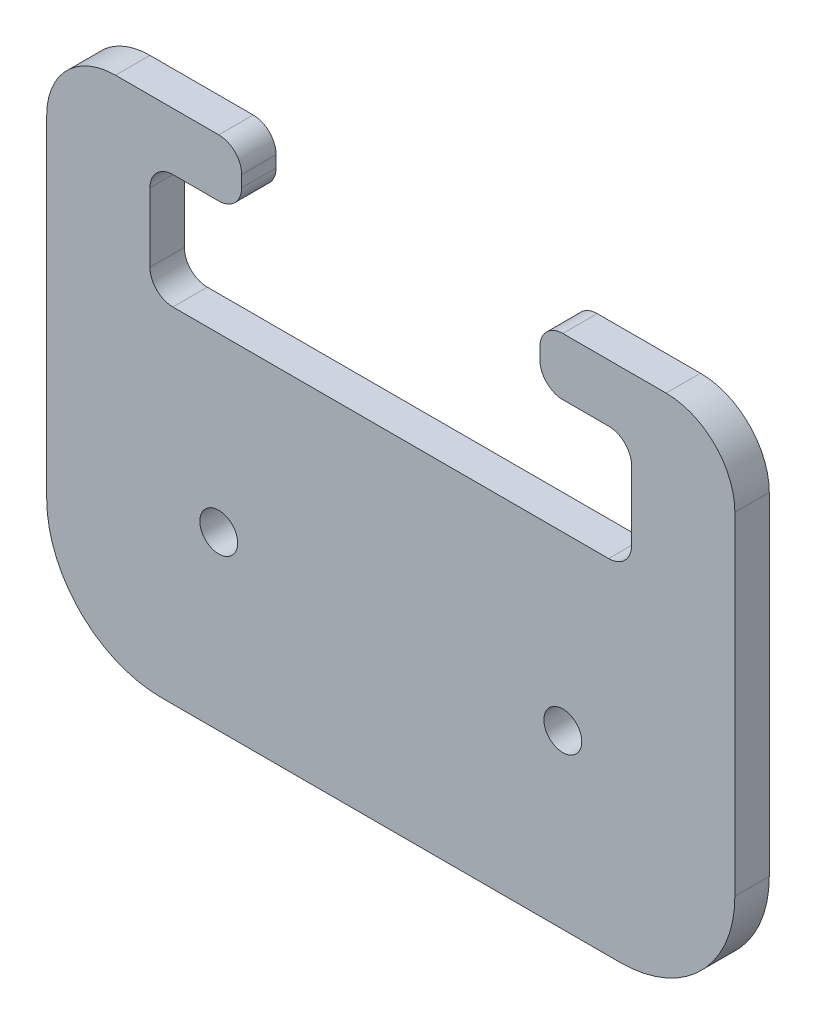
SolidWorks part; units mm, degrees
material "Hexcel AS4C (3000 丝)"
ref_plane "前视基准面" through (0, 0, 0) normal (0, 0, 1) x (1, 0, 0)
ref_plane "上视基准面" through (0, 0, 0) normal (0, 1, 0) x (1, 0, 0)
ref_plane "右视基准面" through (0, 0, 0) normal (1, 0, 0) x (0, 0, -1)
other "Configuration Table"
sketch "草图1" plane through (0, 0, 0) normal (0, 0, 1) x (1, 0, 0)
  line L0 (13, 22.5) -> (30, 22.5)
  line L1 (-30, 22.5) -> (-13, 22.5)
  line L2 (-30, 22.5) -> (-30, -22.5)
  line L3 (-30, -22.5) -> (30, -22.5)
  line L4 (30, 22.5) -> (30, -22.5)
  line L5 (-30, 22.5) -> (30, -22.5) construction
  line L6 (-30, -22.5) -> (30, 22.5) construction
  line L8 (13, 22.5) -> (13, 17.5)
  line L10 (-13, 22.5) -> (-13, 17.5)
  line L11 (21, 17.5) -> (13, 17.5)
  line L12 (21, 17.5) -> (21, 7.5)
  line L13 (21, 7.5) -> (-21, 7.5)
  line L14 (-21, 17.5) -> (-21, 7.5)
  line L15 (-13, 17.5) -> (-21, 17.5)
  point P0 (0, 0)
  dimension "D1" = 45
  dimension "D2" = 60
  dimension "D3" = 5
  dimension "D4" = 17
  dimension "D5" = 17
  dimension "D6" = 9
  dimension "D7" = 9
  dimension "D8" = 10
extrude "凸台-拉伸1" add sketch "草图1" along normal blind 3
fillet "圆角1" radius 6 2 edges at (30, 22.5, 1.5) (-30, 22.5, 1.5)
fillet "圆角2" radius 2 8 edges at (21, 17.5, 1.5) (21, 7.5, 1.5) (-21, 7.5, 1.5) (-21, 17.5, 1.5) (-13, 17.5, 1.5) (-13, 22.5, 1.5) (13, 17.5, 1.5) (13, 22.5, 1.5)
sketch "草图2" plane through (0, 0, 3) normal (0, 0, 1) x (1, 0, 0)
  line L0 (-30, -22.5) -> (30, -22.5) construction
  line L1 (-30, 16.5) -> (-30, -22.5) construction
  circle A0 centre (-15, -7.5) radius 1.65
  circle A1 centre (15, -7.5) radius 1.65
  dimension "D1" = 3.3
  dimension "D2" = 3.3
  dimension "D3" = 15
  dimension "D4" = 15
  dimension "D5" = 30
  dimension "D6" = 15
extrude "切除-拉伸1" cut sketch "草图2" against normal blind 5
fillet "圆角3" radius 10 2 edges at (-30, -22.5, 1.5) (30, -22.5, 1.5)
